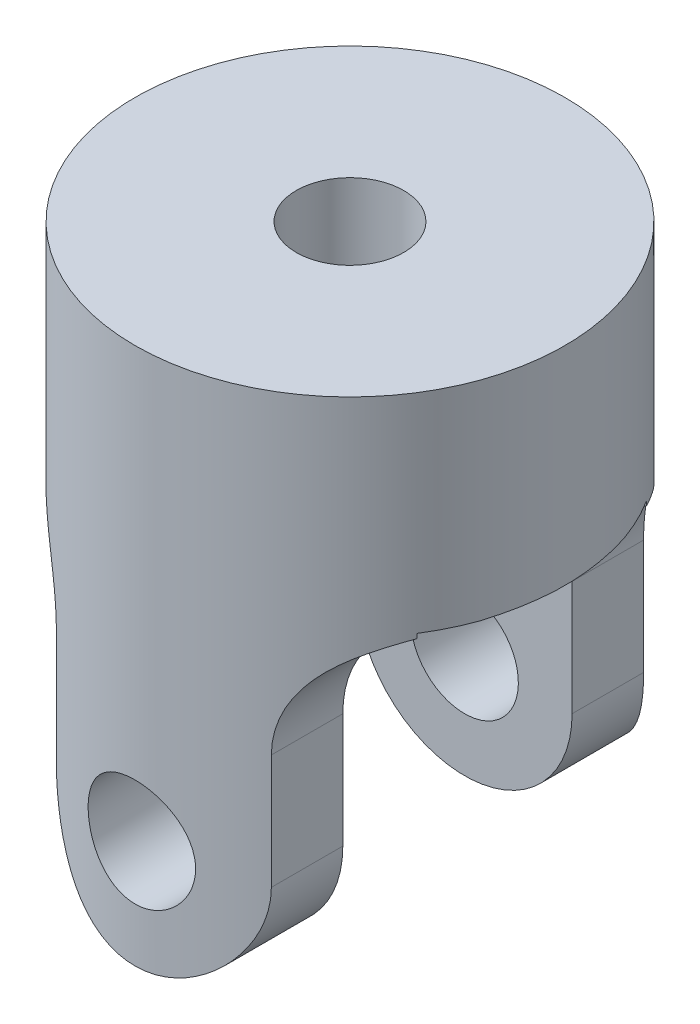
SolidWorks part; units mm, degrees
ref_plane "Front" through (0, 0, 0) normal (0, 0, 1) x (1, 0, 0)
ref_plane "Top" through (0, 0, 0) normal (0, 1, 0) x (-1, 0, 0)
ref_plane "Right" through (0, 0, 0) normal (1, 0, 0) x (0, 0, -1)
sketch "Sketch1" plane through (0, 0, 0) normal (0, 1, 0) x (-1, 0, 0)
  circle A0 centre (0, 0) radius 19.05
  dimension "D1" = 38.1
extrude "Base-Extrude" add sketch "Sketch1" along normal blind 47.625
sketch "Sketch2" plane through (0, 0, 0) normal (0, 0, 1) x (1, 0, 0)
  line L0 (0, 0) -> (0, 23.7435) construction
  line L1 (9.525, 9.525) -> (9.525, 19.685)
  line L2 (-9.525, 9.525) -> (-9.525, 19.685)
  line L3 (19.05, 29.21) -> (19.05, 0)
  line L4 (-19.05, 47.625) -> (-19.05, 0) construction
  line L5 (-19.05, 0) -> (-19.05, 29.21)
  line L6 (19.05, 0) -> (-19.05, 0) construction
  arc A0 (-9.525, 9.525) -> (9.525, 9.525) centre (0, 9.525) ccw
  arc A1 (9.525, 19.685) -> (19.05, 29.21) centre (19.05, 19.685) cw
  arc A2 (-9.525, 19.685) -> (-19.05, 29.21) centre (-19.05, 19.685) ccw
  dimension "D3" = 9.525
  dimension "D2" = 19.05
  dimension "D4" = 29.21
extrude "Cut-Extrude1" cut sketch "Sketch2" against normal through all and the other way through all flip side to cut
sketch "Sketch8" plane through (0, 0, 0) normal (1, 0, 0) x (0, 0, -1)
  line L0 (-19.05, 0) -> (19.05, 0) construction
  line L1 (-10.16, 0) -> (-10.16, 29.1452)
  line L2 (10.16, 29.1452) -> (-10.16, 29.1452)
  line L3 (10.16, 29.1452) -> (10.16, 0)
  line L4 (0, 0) -> (0, 14.3858) construction
  point P4 (0, 0)
  dimension "D1" = 29.1452
  dimension "D2" = 20.32
extrude "Cut-Extrude5" cut sketch "Sketch8" against normal through all and the other way through all flip side to cut
sketch "Sketch11" plane through (0, 0, 0) normal (0, 0, 1) x (1, 0, 0)
  circle A0 centre (0, 9.525) radius 4.7625
  dimension "D1" = 9.525
extrude "Cut-Extrude6" cut sketch "Sketch11" against normal through all and the other way through all
sketch "Sketch12" plane through (0, 47.625, 0) normal (0, 1, 0) x (-1, 0, 0)
  circle A0 centre (0, 0) radius 4.7625
  dimension "D1" = 9.525
extrude "Cut-Extrude7" cut sketch "Sketch12" against normal through all
ref_axis "Axis1" through (0, 97.625, 0) along (0, -1, 0)
